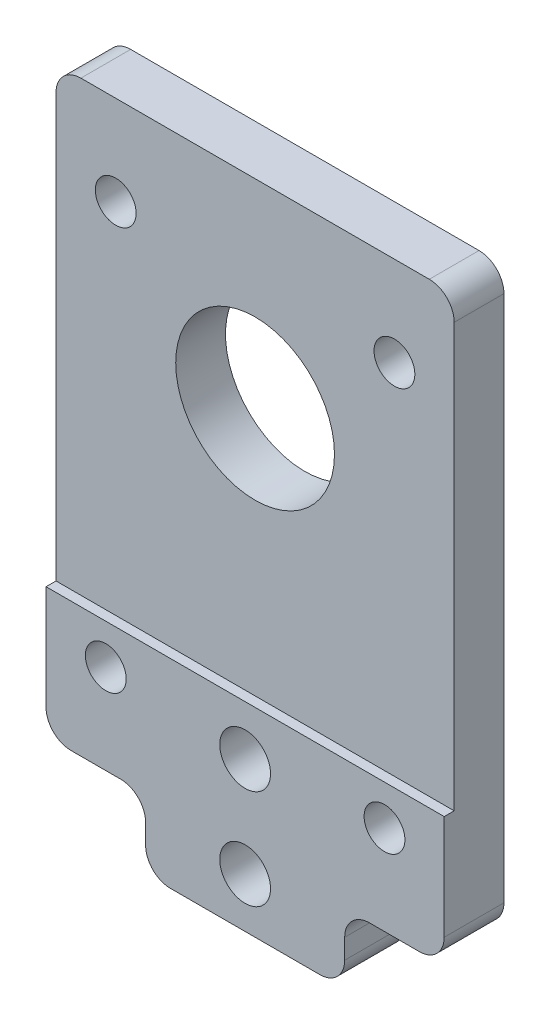
SolidWorks part; units mm, degrees
ref_plane "Front Plane" through (0, 0, 0) normal (0, 0, 1) x (1, 0, 0)
ref_plane "Top Plane" through (0, 0, 0) normal (0, 1, 0) x (1, 0, 0)
ref_plane "Right Plane" through (0, 0, 0) normal (1, 0, 0) x (0, 0, -1)
sketch "Sketch1" plane through (0, 0, 0) normal (0, 0, 1) x (1, 0, 0)
  line L0 (0, -353.8104) -> (0, 17336.7087) construction
  line L1 (-10, -15) -> (-10, 15)
  line L2 (-10, 15) -> (-15, 30)
  line L3 (10, -15) -> (-10, -15)
  line L4 (10, -15) -> (10, 15)
  line L5 (10, 15) -> (15, 30)
  arc A0 (15, 30) -> (-15, 30) centre (0, 30) ccw
  circle A1 centre (0, 0) radius 2.55
  circle A2 centre (0, -10) radius 2.55
  dimension "D1" = 5.1
  dimension "D2" = 5.1
  dimension "D3" = 10
  dimension "D4" = 30
  dimension "D5" = 30
  dimension "D7" = 30
  dimension "D6" = 5
  dimension "D8" = 20
  dimension "D9" = 10
  dimension "D10" = 30
extrude "Boss-Extrude2" add sketch "Sketch1" along normal blind 6
sketch "Sketch7" plane through (0, 0, 0) normal (0, 0, -1) x (-1, 0, 0)
  line L0 (0, -970) -> (0, 49030) construction
  line L1 (-20, 50) -> (20, 50)
  line L2 (-20, 50) -> (-20, -8)
  line L3 (-20, -8) -> (20, -8)
  line L4 (20, 50) -> (20, -8)
  arc A0 (15, 30) -> (-15, 30) centre (0, 30) ccw construction
  dimension "D1" = 40
  dimension "D2" = 58
  dimension "D3" = 20
  dimension "D4" = 20
extrude "Boss-Extrude3" add sketch "Sketch7" against normal blind 6
fillet "Fillet1" radius 2.5 8 edges at (10, -15, 3) (-10, -15, 3) (20, 50, 3) (10, -8, 3) (20, -8, 3) (-20, 50, 3) (-20, -8, 3) (-10, -8, 3)
sketch "Sketch3" plane through (0, 0, 6) normal (0, 0, 1) x (1, 0, 0)
  circle A0 centre (0, 30) radius 7.975
  dimension "D1" = 15.95
  dimension "D2" = 30
extrude "Cut-Extrude2" cut sketch "Sketch3" against normal through all
sketch "Sketch2" plane through (0, 0, 6) normal (0, 0, 1) x (1, 0, 0)
  line L0 (-1009.4328, 41) -> (48990.5672, 41) construction
  line L1 (-1007.6541, 1) -> (48992.3459, 1) construction
  line L2 (-14, -973.06) -> (-14, 49026.94) construction
  line L3 (14, -977.0128) -> (14, 49022.9872) construction
  line L4 (0, -970) -> (0, 49030) construction
  line L5 (-1000, 30) -> (49000, 30) construction
  line L6 (-17.5, 50) -> (17.5, 50) construction
  circle A0 centre (-14, 41) radius 2.05
  circle A1 centre (14, 41) radius 2.05
  circle A2 centre (14, 1) radius 2.05
  circle A3 centre (-14, 1) radius 2.05
  dimension "D3" = 9
  dimension "D4" = 40
  dimension "D5" = 4.1
  dimension "D6" = 4.1
  dimension "D7" = 4.1
  dimension "D8" = 4.1
  dimension "D1" = 14
  dimension "D2" = 14
extrude "Cut-Extrude1" cut sketch "Sketch2" against normal through all
sketch "Sketch6" plane through (0, 0, 6) normal (0, 0, 1) x (1, 0, 0)
  line L0 (-7.5, -15) -> (7.5, -15) construction
  line L1 (-30, 5) -> (30, 5)
  line L2 (-30, 5) -> (-30, 55)
  line L3 (-30, 55) -> (30, 55)
  line L4 (30, 5) -> (30, 55)
  line L5 (-30, 5) -> (30, 55) construction
  line L6 (-30, 55) -> (30, 5) construction
  point P0 (0, 30)
  dimension "D1" = 20
  dimension "D2" = 60
extrude "Cut-Extrude5" cut sketch "Sketch6" against normal blind 1
sketch "Sketch9" plane through (0, 0, 6) normal (0, 0, 1) x (1, 0, 0)
  circle A0 centre (0, -10) radius 2.55
  circle A1 centre (0, 0) radius 2.55
  dimension "D1" = 5.1
  dimension "D2" = 5.1
extrude "Cut-Extrude7" cut sketch "Sketch9" against normal through all
